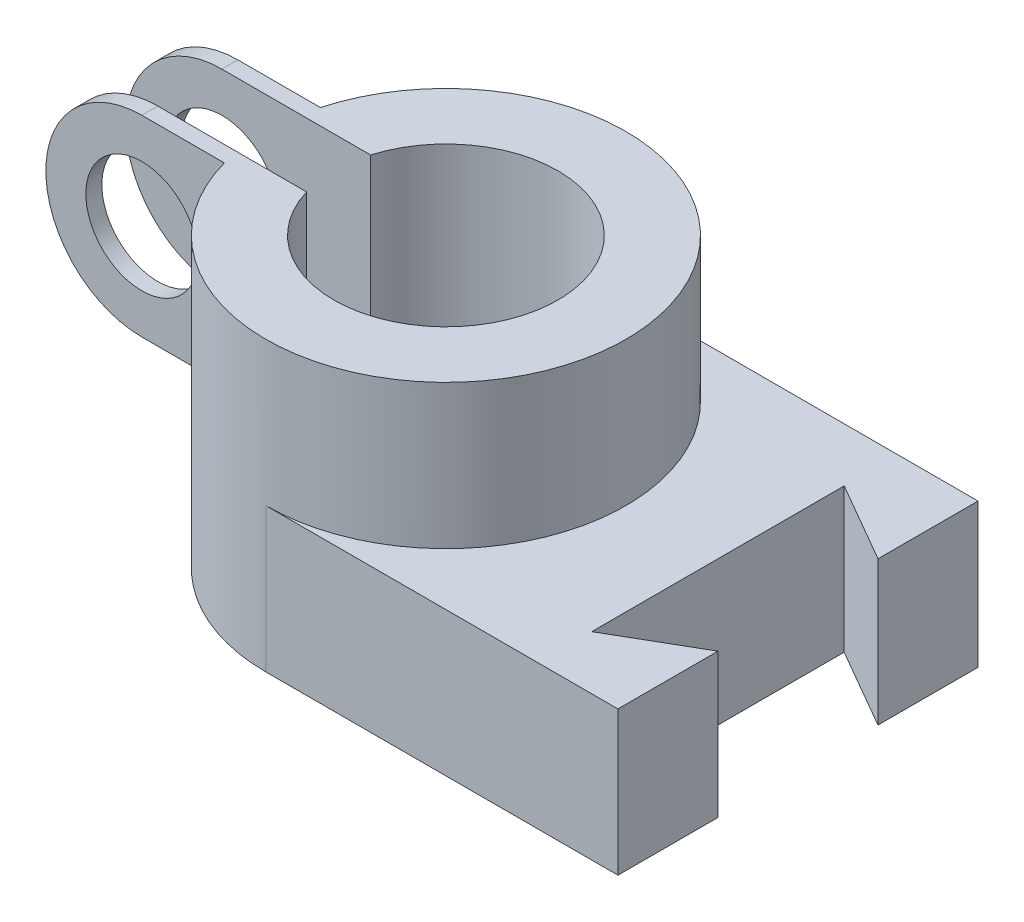
SolidWorks part; units mm, degrees
ref_plane "前视基准面" through (0, 0, 0) normal (0, 0, 1) x (1, 0, 0)
ref_plane "上视基准面" through (0, 0, 0) normal (0, 1, 0) x (1, 0, 0)
ref_plane "右视基准面" through (0, 0, 0) normal (1, 0, 0) x (0, 0, -1)
other "Configuration Table"
sketch "草图1" plane through (0, 0, 0) normal (0, 1, 0) x (1, 0, 0)
  line L0 (0, 0) -> (-36.148, 0) construction
  line L1 (-22.1416, 4) -> (-13.4164, 4)
  line L2 (-22.1416, -4) -> (-13.4164, -4)
  line L3 (0, 22.5) -> (44, 22.5)
  line L4 (0, -22.5) -> (44, -22.5)
  line L5 (44, 22.5) -> (44, -22.5)
  arc A0 (-13.4164, -4) -> (-13.4164, 4) centre (0, 0) ccw
  arc A1 (-22.1416, -4) -> (-22.1416, 4) centre (0, 0) ccw
  dimension "D1" = 28
  dimension "D2" = 45
  dimension "D3" = 8
  dimension "D4" = 44
extrude "凸台-拉伸1" add sketch "草图1" along normal blind 36 contours A1 L1 A0 L2 region at (-14.0201, 0, -16.7799)
extrude "凸台-拉伸2" add sketch "草图1<3>" along normal blind 18 contours A1 L4 L5 L3 region at (30.3568, 0, 0)
sketch "草图1<3>" plane through (0, 0, 0) normal (0, 1, 0) x (1, 0, 0) same geometry as "草图1"
sketch "草图3" plane through (0, 0, 0) normal (0, 0, 1) x (1, 0, 0)
  line L0 (-32, 36) -> (-21.2397, 36)
  line L3 (-32, 12) -> (-21.2397, 12)
  line L4 (-21.2397, 36) -> (-21.2397, 12)
  arc A0 (-32, 36) -> (-32, 12) centre (-32, 24) ccw
  circle A1 centre (-32, 24) radius 7
  point P1 (0, 0)
  dimension "D1" = 24
  dimension "D2" = 14
  dimension "D3" = 32
extrude "凸台-拉伸3" add sketch "草图3" along normal blind 2 from offset 4
extrude "凸台-拉伸4" add sketch "草图3<2>" against normal blind 2 from offset 4 offset against normal yes
sketch "草图3<2>" plane through (0, 0, 0) normal (0, 0, 1) x (1, 0, 0) same geometry as "草图3"
sketch "草图4" plane through (0, 18, 0) normal (0, 1, 0) x (1, 0, 0)
  line L0 (0, 0) -> (60.7705, 0) construction
  line L1 (44, 10) -> (34, 15.7735)
  line L2 (44, 22.5) -> (44, -22.5) construction
  line L3 (34, 15.7735) -> (34, -15.7735)
  line L4 (44, 10) -> (44, -10)
  line L5 (44, -10) -> (34, -15.7735)
  point P10 (34, 0)
  point P11 (44, 0)
  dimension "D1" = 20
  dimension "D2" = 10
  dimension "D3" = 60
extrude "切除-拉伸1" cut sketch "草图4" against normal through all
